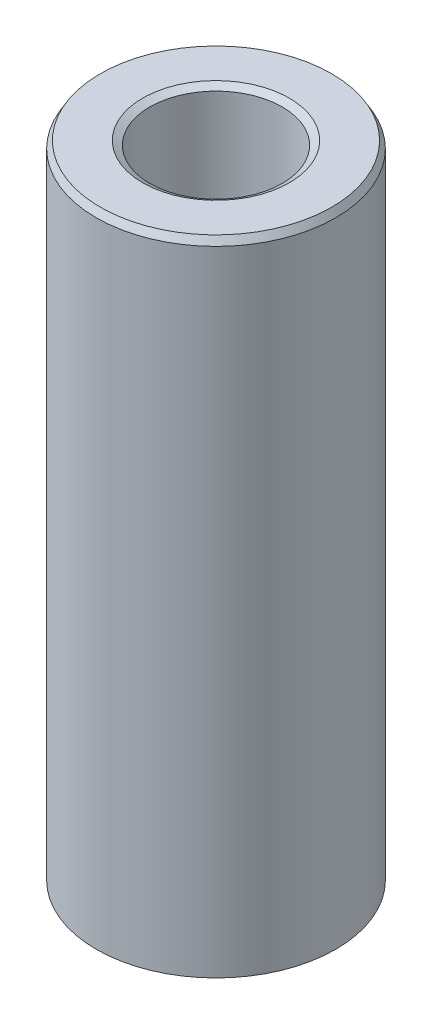
SolidWorks part; units mm, degrees
ref_plane "Front Plane" through (0, 0, 0) normal (0, 0, 1) x (1, 0, 0)
ref_plane "Top Plane" through (0, 0, 0) normal (0, 1, 0) x (1, 0, 0)
ref_plane "Right Plane" through (0, 0, 0) normal (1, 0, 0) x (0, 0, -1)
sketch "Sketch1" plane through (0, 0, 0) normal (0, 1, 0) x (1, 0, 0)
  circle A0 centre (0, 0) radius 52.5
  dimension "SLEEVE_OD" = 105
extrude "Boss-Extrude1" add sketch "Sketch1" along normal blind 282.61
sketch "Sketch2" plane through (0, 0, 0) normal (0, 1, 0) x (1, 0, 0)
  circle A0 centre (0, 0) radius 29.0419
  dimension "BORE_D" = 58.0838
extrude "Cut-Extrude1" cut sketch "Sketch2" along normal through all
chamfer "Chamfer1" distance 3.1044 angle 30 4 edges at (0, 282.61, 29.0419) (0, 0, 29.0419) (0, 0, 52.5) (0, 282.61, 52.5) first distance on face at (0, 282.61, 29.0419) first distance on face at (0, 0, 29.0419) first distance on face at (0, 282.61, 52.5)
